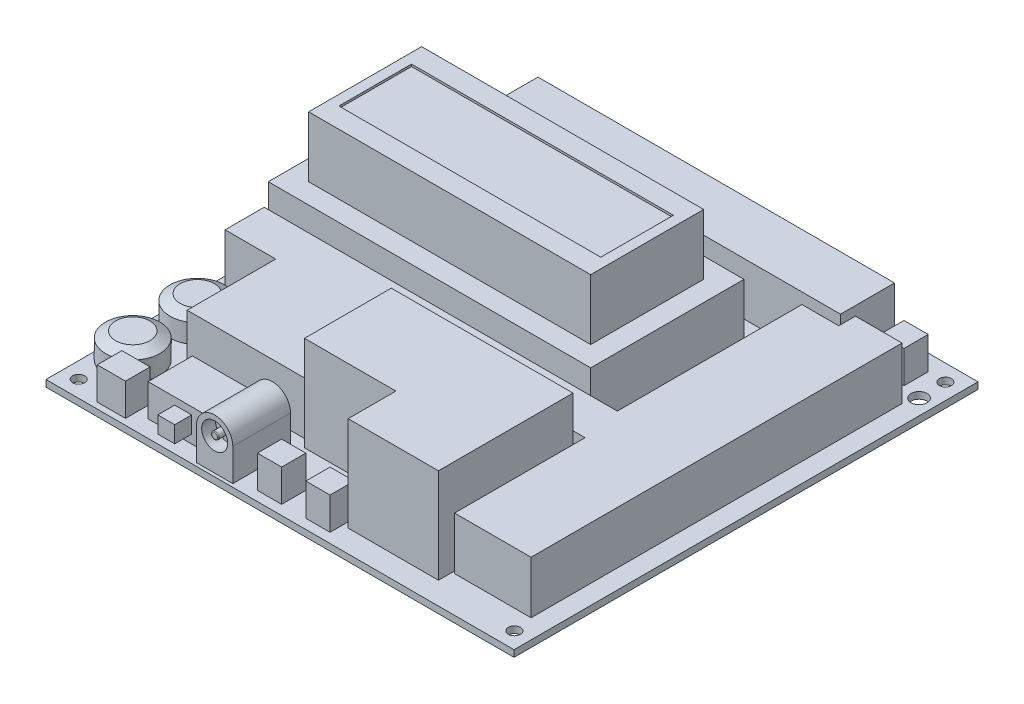
SolidWorks part; units mm, degrees
ref_plane "Front Plane" through (0, 0, 0) normal (0, 0, 1) x (1, 0, 0)
ref_plane "Top Plane" through (0, 0, 0) normal (0, 1, 0) x (1, 0, 0)
ref_plane "Right Plane" through (0, 0, 0) normal (1, 0, 0) x (0, 0, -1)
sketch "Sketch1" plane through (0, 0, 0) normal (0, 1, 0) x (1, 0, 0)
  line L0 (0, 0) -> (0, 33.841) construction
  line L1 (-58, 57.5) -> (58, 57.5)
  line L2 (-58, 57.5) -> (-58, -57.5)
  line L3 (-58, -57.5) -> (58, -57.5)
  line L4 (58, 57.5) -> (58, -57.5)
  line L5 (-58, 57.5) -> (58, -57.5) construction
  line L6 (-58, -57.5) -> (58, 57.5) construction
  line L7 (0, 0) -> (35.7678, 0) construction
  circle A0 centre (54, 53.4) radius 1.5
  circle A1 centre (54, -53.4) radius 1.5
  circle A2 centre (-54, 53.4) radius 1.5
  circle A3 centre (-54, -53.4) radius 1.5
  point P0 (0, 0)
  dimension "D5" = 3
  dimension "D1" = 115
  dimension "D2" = 116
  dimension "D3" = 108
  dimension "D4" = 106.8
sheet metal parameters "Sheet-Metal1" thickness 1.65 parameters "D1"=245.3911
base flange "Base-Flange1" sketch "Sketch1" thickness 1.65 reverse thickness direction yes parameters "D1"=245.3911
sketch "Sketch3" plane through (0, 1.65, 0) normal (0, 1, 0) x (1, 0, 0)
  line L1 (-57.9, 35.5) -> (22, 35.5)
  line L2 (-57.9, 35.5) -> (-57.9, -2.5)
  line L3 (-57.9, -2.5) -> (22, -2.5)
  line L4 (22, 35.5) -> (22, -2.5)
  line L5 (58, 57.5) -> (-58, 57.5) construction
  line L6 (-58, 57.5) -> (-58, -57.5) construction
  dimension "D1" = 22
  dimension "D2" = 60
  dimension "D3" = 80
  dimension "D4" = 0.1
extrude "Extrude1" add sketch "Sketch3" along normal blind 15
sketch "Sketch4" plane through (0, 16.65, 0) normal (0, 1, 0) x (1, 0, 0)
  line L8 (-52.9, 30.5) -> (-52.9, 2.5)
  line L9 (-52.9, 2.5) -> (17, 2.5)
  line L10 (17, 2.5) -> (17, 30.5)
  line L11 (17, 30.5) -> (-52.9, 30.5)
  line L12 (-52.9, 30.5) -> (-52.9, 2.5)
  line L13 (-52.9, 2.5) -> (17, 2.5)
  line L14 (17, 2.5) -> (17, 30.5)
  line L15 (17, 30.5) -> (-52.9, 30.5)
  dimension "D1" = 5
extrude "Extrude2" add sketch "Sketch4" along normal blind 15
sketch "Sketch6" plane through (0, 31.65, 0) normal (0, 1, 0) x (1, 0, 0)
  line L8 (17, 2.5) -> (17, 30.5) construction
  line L9 (-52.9, 30.5) -> (-52.9, 2.5) construction
  line L12 (12, 25.5) -> (-47.9, 25.5)
  line L13 (-47.9, 25.5) -> (-47.9, 7.5)
  line L14 (-47.9, 7.5) -> (12, 7.5)
  line L15 (12, 7.5) -> (12, 25.5)
  line L16 (14.5, 25.5) -> (-50.4, 25.5)
  line L17 (-50.4, 25.5) -> (-50.4, 7.5)
  line L18 (-50.4, 7.5) -> (14.5, 7.5)
  line L19 (14.5, 7.5) -> (14.5, 25.5)
  dimension "D2" = 2.5
  dimension "D3" = 2.5
  dimension "D1" = 5
extrude "Display!" cut sketch "Sketch6" against normal blind 0.53 normal cut yes
sketch "Sketch7" plane through (0, 0, 0) normal (0, -1, 0) x (1, 0, 0)
  line L1 (-57.9, 20.5) -> (33.1, 20.5)
  line L2 (-57.9, 20.5) -> (-57.9, -39.5)
  line L3 (-57.9, -39.5) -> (33.1, -39.5)
  line L4 (33.1, 20.5) -> (33.1, -39.5)
  line L5 (58, -57.5) -> (-58, -57.5) construction
  line L6 (-58, -57.5) -> (-58, 57.5) construction
  dimension "D1" = 91
  dimension "D2" = 60
  dimension "D3" = 18
  dimension "D4" = 0.1
extrude "Wiring Board" add sketch "Sketch7" along normal blind 15
sketch "Sketch8" plane through (0, -15, 0) normal (0, -1, 0) x (1, 0, 0)
  line L0 (-57.9, 20.5) -> (-57.9, -39.5) construction
  line L1 (-43.9, 9.2) -> (-36.9, 9.2)
  line L2 (-43.9, 9.2) -> (-43.9, -10.8)
  line L3 (-43.9, -10.8) -> (-36.9, -10.8)
  line L4 (-36.9, 9.2) -> (-36.9, -10.8)
  line L5 (33.1, 20.5) -> (-57.9, 20.5) construction
  dimension "D1" = 20
  dimension "D2" = 7
  dimension "D3" = 14
  dimension "D4" = 11.3
extrude "Extrude5" add sketch "Sketch8" along normal blind 7.5
sketch "Sketch9" plane through (-58, 0, 0) normal (-1, 0, 0) x (0, 0, 1)
  line L0 (-39.5, -15) -> (-39.5, 0) construction
  line L1 (-29.5, -3.1) -> (-19, -3.1)
  line L2 (-29.5, -3.1) -> (-29.5, -11.6)
  line L3 (-29.5, -11.6) -> (-19, -11.6)
  line L4 (-19, -3.1) -> (-19, -11.6)
  line L5 (20.5, -15) -> (-39.5, -15) construction
  line L6 (-27, -5.6) -> (-21.5, -5.6)
  line L7 (-21.5, -5.6) -> (-21.5, -9.1)
  line L8 (-27, -9.1) -> (-21.5, -9.1)
  line L9 (-27, -5.6) -> (-27, -9.1)
  point P4 (-39.5, -7.5)
  dimension "D1" = 8.5
  dimension "D2" = 10.5
  dimension "D3" = 10
  dimension "D4" = 3.4
  dimension "D5" = 2.5
extrude "USB" cut sketch "Sketch9" against normal blind 7.5 normal cut yes
chamfer "Chamfer1" distance 2 angle 45 2 edges at (-54.2, -3.1, -19) (-54.2, -3.1, -29.5)
sketch "Sketch10" plane through (0, 1.65, 0) normal (0, 1, 0) x (1, 0, 0)
  line L0 (-58, 57.5) -> (-58, -57.5) construction
  line L1 (-58, -57.5) -> (58, -57.5) construction
  circle A0 centre (-51.5, -26.5) radius 6.75
  circle A1 centre (-51.5, -42.5) radius 6.75
  dimension "D1" = 13.5
  dimension "D3" = 16
  dimension "D2" = 6.5
  dimension "D4" = 15
extrude "Potentiometers" add sketch "Sketch10" along normal blind 6.2
sketch "Sketch11" plane through (0, 1.65, 0) normal (0, 1, 0) x (1, 0, 0)
  line L0 (-26.092, -53.3) -> (-23.1, -53.3)
  line L1 (-46.8, -49.9) -> (-39.8, -49.9)
  line L2 (-46.8, -49.9) -> (-46.8, -56)
  line L3 (-46.8, -56) -> (-39.8, -56)
  line L4 (-39.8, -49.9) -> (-39.8, -56)
  line L5 (-36.9, -42.3) -> (-23.1, -42.3)
  line L6 (-36.9, -42.3) -> (-36.9, -53.3)
  line L7 (-36.9, -53.3) -> (-30.292, -53.3)
  line L8 (-23.1, -42.3) -> (-23.1, -53.3)
  line L10 (-30.292, -53.3) -> (-30.292, -57.5)
  line L11 (-30.292, -57.5) -> (-26.092, -57.5)
  line L12 (-26.092, -53.3) -> (-26.092, -57.5)
  line L13 (-21.5, -42.4) -> (-12.5, -42.4)
  line L14 (-21.5, -42.4) -> (-21.5, -56.7)
  line L15 (-21.5, -56.7) -> (-12.5, -56.7)
  line L16 (-12.5, -42.4) -> (-12.5, -56.7)
  line L17 (-8, -49.1) -> (-2, -49.1)
  line L18 (-8, -49.1) -> (-8, -55.1)
  line L19 (-8, -55.1) -> (-2, -55.1)
  line L20 (-2, -49.1) -> (-2, -55.1)
  line L21 (4, -49.1) -> (10, -49.1)
  line L22 (4, -49.1) -> (4, -55.1)
  line L23 (4, -55.1) -> (10, -55.1)
  line L24 (10, -49.1) -> (10, -55.1)
  line L25 (-58, -44.32) -> (-58, -57.5) construction
  line L26 (-58, -57.5) -> (58, -57.5) construction
  line L27 (-58, -28.32) -> (-58, -40.68) construction
  line L28 (-58, 57.5) -> (-58, -24.68) construction
  line L29 (58, 57.5) -> (-58, 57.5) construction
  line L30 (43.66, 53.5) -> (49.66, 53.5)
  line L31 (43.66, 53.5) -> (43.66, 47.5)
  line L32 (43.66, 47.5) -> (49.66, 47.5)
  line L33 (49.66, 53.5) -> (49.66, 47.5)
  line L34 (58, -57.5) -> (58, 57.5) construction
  line L35 (-58, 57.5) -> (-58, -24.68) construction
  line L36 (-55.82, 47.8) -> (-53.82, 47.8)
  line L37 (-55.82, 47.8) -> (-55.82, 42.8)
  line L38 (-55.82, 42.8) -> (-53.82, 42.8)
  line L39 (-53.82, 47.8) -> (-53.82, 42.8)
  line L40 (-53.52, 47.8) -> (-51.52, 47.8)
  line L41 (-53.52, 47.8) -> (-53.52, 42.8)
  line L42 (-53.52, 42.8) -> (-51.52, 42.8)
  line L43 (-51.52, 47.8) -> (-51.52, 42.8)
  dimension "D1" = 7
  dimension "D2" = 13.8
  dimension "D3" = 11
  dimension "D4" = 7.6
  dimension "D5" = 11.2
  dimension "D6" = 1.5
  dimension "D7" = 21.1
  dimension "D8" = 4.2
  dimension "D9" = 9
  dimension "D10" = 14.3
  dimension "D11" = 36.5
  dimension "D12" = 0.8
  dimension "D13" = 6
  dimension "D14" = 2.4
  dimension "D15" = 50
  dimension "D16" = 6
  dimension "D17" = 4
  dimension "D18" = 8.34
  dimension "D19" = 2.18
  dimension "D20" = 2
  dimension "D21" = 0.3
  dimension "D22" = 5
  dimension "D23" = 14.7
extrude "Keep Accessible!!" add sketch "Sketch11" along normal blind 8
sketch "Sketch12" plane through (0, 1.65, 0) normal (0, 1, 0) x (1, 0, 0)
  line L0 (-48.9486, 53.6703) -> (-48.9486, 44.8322)
  line L1 (-48.9486, 44.8322) -> (-35.8339, 44.8322)
  line L2 (-35.8339, 44.8322) -> (-35.8339, 41.9811)
  line L3 (-35.8339, 41.9811) -> (37.2945, 41.9811)
  line L4 (37.2945, 41.9811) -> (39.4328, 41.9811)
  line L5 (39.4328, 41.9811) -> (39.4328, 53.6703)
  line L6 (39.4328, 53.6703) -> (39.4328, 55.3809)
  line L7 (39.4328, 55.3809) -> (-48.9486, 55.3809)
  line L8 (-48.9486, 55.3809) -> (-48.9486, 53.6703)
  line L9 (41.7136, 43.4066) -> (41.7136, 39.2727)
  line L10 (41.7136, 39.2727) -> (32.5904, 39.2727)
  line L11 (32.5904, 39.2727) -> (32.5904, -6.4861)
  line L12 (32.5904, -6.4861) -> (-54.9357, -6.4861)
  line L13 (-54.9357, -6.4861) -> (-54.9357, -16.1795)
  line L14 (-54.9357, -16.1795) -> (-42.3912, -16.1795)
  line L15 (-42.3912, -16.1795) -> (-42.3912, -38.1323)
  line L16 (-42.3912, -38.1323) -> (-13.3109, -38.1323)
  line L17 (-13.3109, -38.1323) -> (-13.3109, -16.1795)
  line L18 (-13.3109, -16.1795) -> (34.301, -16.1795)
  line L19 (34.301, -16.1795) -> (34.301, -48.5385)
  line L20 (34.301, -48.5385) -> (53.2602, -48.5385)
  line L21 (53.2602, -48.5385) -> (53.2602, 43.4066)
  line L22 (53.2602, 43.4066) -> (41.7136, 43.4066)
extrude "Extrude9" add sketch "Sketch12" along normal blind 13
sketch "Sketch13" plane through (0, 1.65, 0) normal (0, 1, 0) x (1, 0, 0)
  line L0 (-11.3152, -18.6028) -> (-11.3152, -40.128)
  line L1 (-11.3152, -40.128) -> (11.3503, -40.128)
  line L2 (11.3503, -40.128) -> (11.3503, -51.9597)
  line L3 (11.3503, -51.9597) -> (33.7308, -51.9597)
  line L4 (33.7308, -51.9597) -> (33.7308, -18.6028)
  line L5 (33.7308, -18.6028) -> (-11.3152, -18.6028)
extrude "Hot! Voltage Regs" add sketch "Sketch13" along normal blind 23.5
sketch "Sketch14" plane through (0, 0, 56.7) normal (0, 0, 1) x (1, 0, 0)
  line L0 (-21.5, 9.65) -> (-12.5, 9.65) construction
  circle A0 centre (-17, 9.65) radius 4.5
extrude "Extrude10" add sketch "Sketch14" against normal up to surface (14.3 mm away) up to face at (-17, 5.65, 42.4)
sketch "Sketch15" plane through (0, 0, 56.7) normal (0, 0, 1) x (1, 0, 0)
  line L0 (-36.9, 1.65) -> (-30.292, 1.65) construction
  line L1 (-31.1638, 10.5463) -> (-25.2139, 10.5463)
  line L2 (-31.1638, 10.5463) -> (-31.1638, 7.9077)
  line L3 (-31.1638, 7.9077) -> (-25.2139, 7.9077)
  line L4 (-25.2139, 10.5463) -> (-25.2139, 7.9077)
  line L5 (-31.1638, 1.65) -> (-25.2139, 1.65)
  line L6 (-31.1638, 1.65) -> (-31.1638, 3.783)
  line L7 (-31.1638, 3.783) -> (-25.2139, 3.783)
  line L8 (-25.2139, 1.65) -> (-25.2139, 3.783)
  circle A0 centre (-17, 9.65) radius 3.2198
  circle A1 centre (-17, 9.65) radius 0.8963
extrude "Extrude11" cut sketch "Sketch15" against normal up to surface (3.4 mm away) and the other way blind 10 normal cut yes up to face at (-33.596, 5.65, 53.3)
fillet "Fillet1" radius 0.2 5 edges at (-57.9, -5.6, -24.25) (-57.9, -7.35, -21.5) (-57.9, -9.1, -24.25) (-57.9, -7.35, -27) (-17.8963, 9.65, 56.7)
chamfer "Chamfer2" distance 1.5 distance2 2.5 2 edges at (-51.5, 7.85, 33.25) (-51.5, 7.85, 49.25) first distance on face at (-51.5, 7.85, 33.25) first distance on face at (-51.5, 7.85, 49.25)
sketch "Sketch16" plane through (0, 1.65, 0) normal (0, 1, 0) x (1, 0, 0)
  line L0 (58, -57.5) -> (58, 57.5) construction
  line L1 (58, 57.5) -> (-58, 57.5) construction
  circle A0 centre (54.2, 46.7) radius 2
  dimension "D1" = 4
  dimension "D2" = 3.8
  dimension "D3" = 10.8
extrude "Extrude12" cut sketch "Sketch16" against normal blind 10 normal cut yes
flat pattern "Flat-Pattern1" [suppressed]
sketch "Bend-Lines1" plane through (0, 0, 0) normal (0, 1, 0) x (-1, 0, 0)
